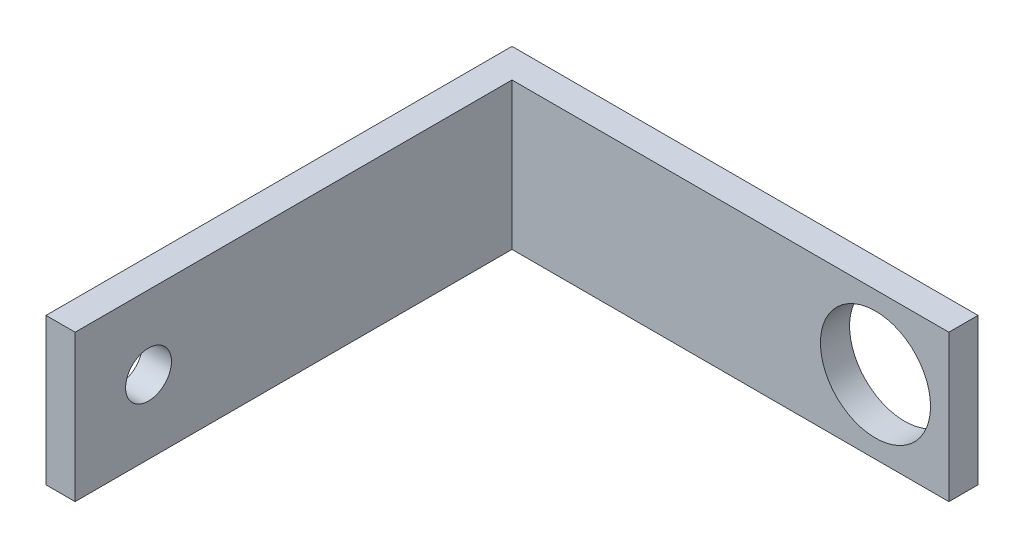
SolidWorks part; units mm, degrees
ref_plane "Front Plane" through (0, 0, 0) normal (0, 0, 1) x (1, 0, 0)
ref_plane "Top Plane" through (0, 0, 0) normal (0, 1, 0) x (1, 0, 0)
ref_plane "Right Plane" through (0, 0, 0) normal (1, 0, 0) x (0, 0, -1)
sketch "Sketch1" plane through (0, 0, 0) normal (0, 1, 0) x (1, 0, 0)
  line L0 (-20.6062, 0) -> (0, 0) construction
  line L1 (-4, 19.8125) -> (4, 19.8125)
  line L2 (-4, 19.8125) -> (-4, 21.4) construction
  line L3 (-4, 21.4) -> (4, 21.4)
  line L4 (4, 19.8125) -> (4, 21.4)
  line L5 (-4, 19.8125) -> (4, 21.4) construction
  line L6 (-4, 21.4) -> (4, 19.8125) construction
  line L7 (-21.4, 4) -> (-19.8125, 4) construction
  line L8 (-21.4, 4) -> (-21.4, -4)
  line L9 (-21.4, -4) -> (-19.8125, -4)
  line L10 (-19.8125, 4) -> (-19.8125, -4)
  line L11 (-21.4, 4) -> (-19.8125, -4) construction
  line L12 (-21.4, -4) -> (-19.8125, 4) construction
  line L13 (0, 0) -> (0, 20.6062) construction
  line L14 (-19.8125, 4) -> (-19.8125, 19.8125)
  line L15 (-19.8125, 19.8125) -> (-4, 19.8125)
  line L16 (-4, 21.4) -> (-21.4, 21.4)
  line L17 (-21.4, 21.4) -> (-21.4, 4)
  arc A0 (-19.8125, 4) -> (-4, 19.8125) centre (-4, 4) cw construction
  arc A1 (-21.4, 4) -> (-4, 21.4) centre (-4, 4) cw construction
  point P0 (0, 20.6062)
  point P5 (-20.6062, 0)
  dimension "D3" = 25.4
  dimension "D1" = 1.5875
  dimension "D2" = 8
extrude "Boss-Extrude1" add sketch "Sketch1" along normal mid plane 8 contours L10 L7 L8 L9 | L1 L4 L3 L2 region at (-11.9062, 0, -20.1717)
sketch "Sketch2" plane through (-19.8125, 0, 0) normal (1, 0, 0) x (0, 0, -1)
  circle A0 centre (0, 0) radius 1.25
  dimension "D1" = 2.5
extrude "Cut-Extrude1" cut sketch "Sketch2" against normal through all
sketch "Sketch3" plane through (0, 0, -19.8125) normal (0, 0, 1) x (1, 0, 0)
  circle A0 centre (0, 0) radius 3
  dimension "D1" = 6
extrude "Cut-Extrude2" cut sketch "Sketch3" against normal through all
